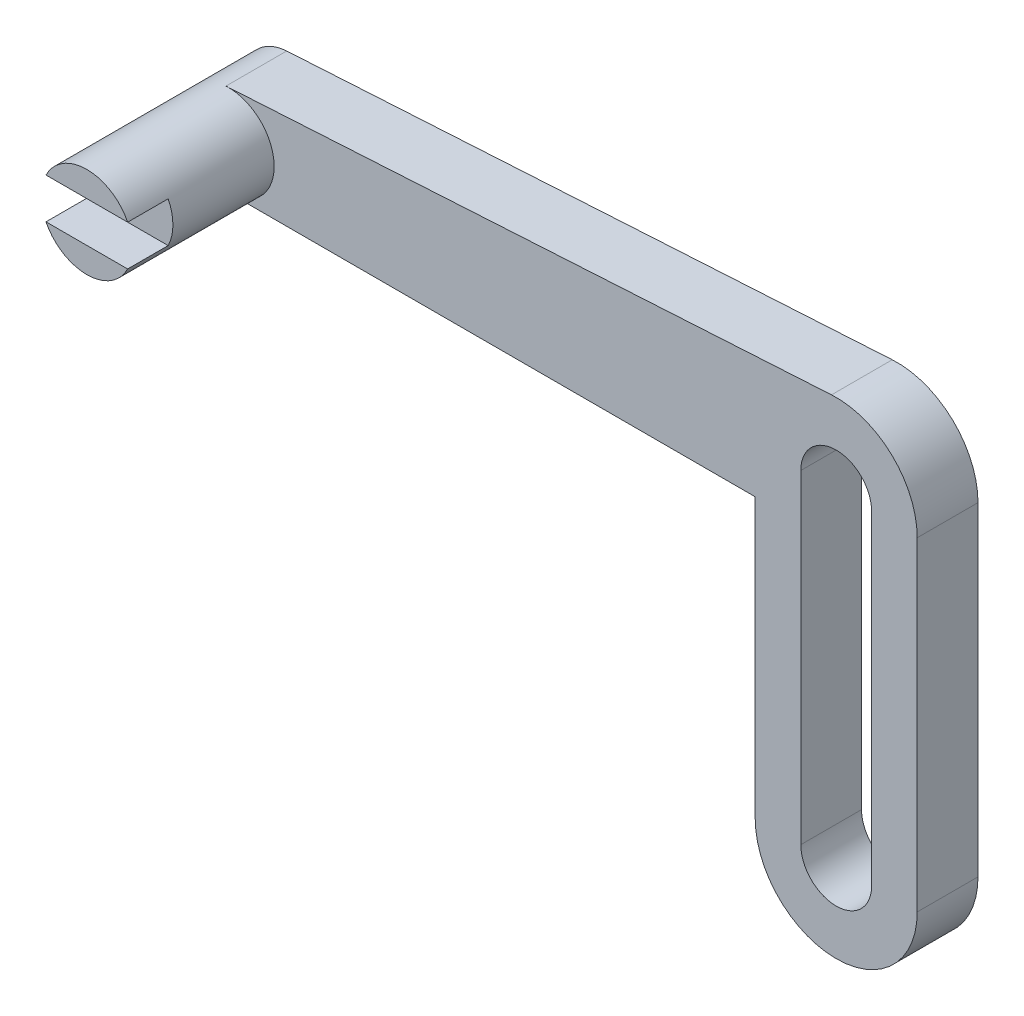
SolidWorks part; units mm, degrees
ref_plane "前视基准面" through (0, 0, 0) normal (0, 0, 1) x (1, 0, 0)
ref_plane "上视基准面" through (0, 0, 0) normal (0, 1, 0) x (1, 0, 0)
ref_plane "右视基准面" through (0, 0, 0) normal (1, 0, 0) x (0, 0, -1)
sketch "草图1" plane through (0, 0, 0) normal (0, 0, 1) x (1, 0, 0)
  line L0 (0, -2.25) -> (26, -2.25)
  line L1 (0, 0) -> (30, 0) construction
  line L2 (-0.1313, 2.2462) -> (29.7667, 3.9932)
  line L3 (34, 0) -> (34, -20)
  line L4 (34, -20) -> (26, -20)
  line L5 (26, -20) -> (26, -2.25)
  line L6 (31.75, -16) -> (31.75, 0)
  line L7 (28.25, 0) -> (28.25, -16)
  line L8 (30, 0) -> (30, -16) construction
  circle A0 centre (0, 0) radius 2.25
  circle A2 centre (30, 0) radius 4
  circle A3 centre (30, 0) radius 1.75
  circle A4 centre (30, -16) radius 1.75
  dimension "D1" = 4.5
  dimension "D5" = 8
  dimension "D6" = 3.5
  dimension "D7" = 3.5
  dimension "D2" = 30
  dimension "D3" = 8
  dimension "D4" = 20
  dimension "D8" = 16
extrude "凸台-拉伸1" add sketch "草图1" along normal blind 3 contours A0 | A0 L1 | L1 A0 | A2 region at (1.886, -1.886, 0) region at (0, 0, 0) region at (32.669, 2.8295, 0)
extrude "凸台-拉伸2" add sketch "草图1<3>" along normal blind 10 contours A0 region at (0, 0, 0)
sketch "草图1<3>" plane through (0, 0, 0) normal (0, 0, 1) x (1, 0, 0) same geometry as "草图1"
sketch "草图2" plane through (0, 0, 10) normal (0, 0, 1) x (1, 0, 0)
  line L1 (2.5, 1) -> (-2.5, 1)
  line L2 (2.5, 1) -> (2.5, -1)
  line L3 (2.5, -1) -> (-2.5, -1)
  line L4 (-2.5, 1) -> (-2.5, -1)
  line L5 (2.5, 1) -> (-2.5, -1) construction
  line L6 (2.5, -1) -> (-2.5, 1) construction
  point P0 (0, 0)
  dimension "D1" = 2
  dimension "D2" = 5
extrude "切除-拉伸1" cut sketch "草图2" against normal blind 2
fillet "圆角1" radius 4 2 edges at (26, -20, 1.5) (34, -20, 1.5)
